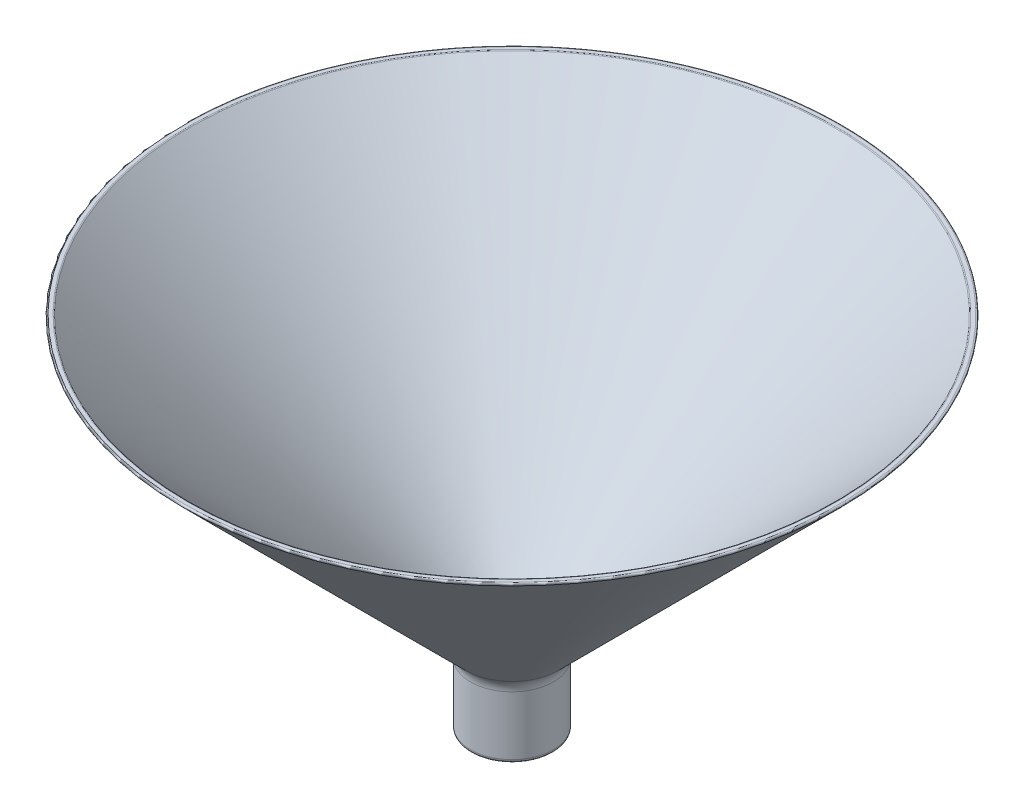
SolidWorks part; units mm, degrees
ref_plane "Front Plane" through (0, 0, 0) normal (0, 0, 1) x (1, 0, 0)
ref_plane "Top Plane" through (0, 0, 0) normal (0, 1, 0) x (1, 0, 0)
ref_plane "Right Plane" through (0, 0, 0) normal (1, 0, 0) x (0, 0, -1)
sketch "Sketch1" plane through (0, 0, 0) normal (0, 0, 1) x (1, 0, 0)
  line L0 (0, 0) -> (6, 0) construction
  line L1 (10, 6.9282) -> (10, 20)
  line L2 (10, 20) -> (90, 100)
  line L3 (0, 0) -> (0, 100) construction
  line L7 (90, 100) -> (92.1213, 100)
  line L9 (6, 0) -> (10, 6.9282)
  line L10 (11.5, 6.5263) -> (11.5, 19.3787)
  line L11 (11.5, 19.3787) -> (92.1213, 100)
  line L12 (11.5, 19.3787) -> (90.6213, 98.5) construction
  line L13 (6, 0) -> (11.5, 0)
  line L14 (7.299, -0.75) -> (11.5, 6.5263) construction
  line L15 (90.6213, 98.5) -> (92.1213, 98.5) construction
  line L16 (11.5, 6.5263) -> (11.5, 0)
  dimension "D1" = 10
  dimension "D2" = 20
  dimension "D3" = 135
  dimension "D4" = 100
  dimension "D6" = 6
  dimension "D7" = 60
  dimension "D5" = 1.5
revolve "Revolve1" add sketch "Sketch1" angle 360 about L3
fillet "Fillet1" radius 5 2 edges at (0, 19.3787, -11.5) (0, 20, -10)
fillet "Fillet2" radius 0.4 2 edges at (0, 100, -90) (0, 100, -92.1213)
fillet "Fillet3" radius 1 1 edges at (0, 0, -11.5)
